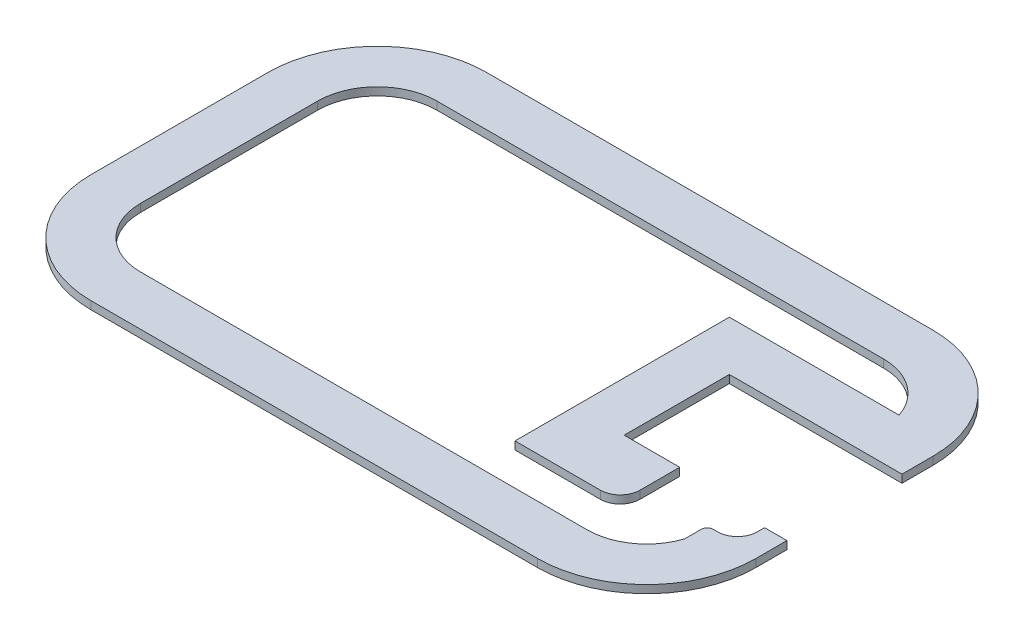
SolidWorks part; units mm, degrees
ref_plane "Front Plane" through (0, 0, 0) normal (0, 0, 1) x (1, 0, 0)
ref_plane "Top Plane" through (0, 0, 0) normal (0, 1, 0) x (1, 0, 0)
ref_plane "Right Plane" through (0, 0, 0) normal (1, 0, 0) x (0, 0, -1)
sketch "Sketch1" plane through (0, 0, 0) normal (0, 1, 0) x (1, 0, 0)
  line L0 (285.2957, -100.4595) -> (285.2957, -116.0895)
  line L1 (5.2657, 28.1705) -> (230.2957, 28.1705)
  line L2 (-49.7343, -26.8295) -> (-49.7343, -116.0895)
  line L3 (5.2657, -171.0895) -> (230.2957, -171.0895)
  line L4 (285.2957, -26.8295) -> (285.2957, -42.4595)
  line L5 (198.2957, -42.4595) -> (285.2957, -42.4595)
  line L6 (198.2957, -42.4595) -> (198.2957, -95.4595)
  line L7 (274.0453, -100.4595) -> (285.2957, -100.4595)
  line L8 (258.7949, -125.4595) -> (258.7949, -125.4595)
  line L9 (5.2657, -146.0895) -> (230.2957, -146.0895)
  line L10 (-24.7343, -26.8295) -> (-24.7343, -116.0895)
  line L11 (5.2657, 3.1705) -> (230.2957, 3.1705)
  line L12 (258.7949, -17.4595) -> (258.7949, -17.4595)
  line L13 (173.2957, -17.4595) -> (258.7949, -17.4595)
  line L14 (173.2957, -17.4595) -> (173.2957, -125.4595)
  line L15 (198.2957, -42.4595) -> (198.2957, -100.4595) construction
  line L16 (274.0453, -100.4595) -> (274.0453, -104.0895)
  line L17 (258.7949, -125.4595) -> (258.7949, -117.0895)
  line L18 (198.2957, -100.4595) -> (285.2957, -100.4595) construction
  line L19 (173.2957, -125.4595) -> (258.7949, -125.4595) construction
  line L20 (173.2957, -125.4595) -> (188.2957, -125.4595)
  line L21 (173.2957, -17.4595) -> (173.2957, -125.4595) construction
  line L22 (264.0453, -114.0895) -> (261.7949, -114.0895)
  line L23 (226.2957, -52.3368) -> (226.2957, -142.322) construction
  line L24 (198.2957, -95.4595) -> (226.2957, -95.4595)
  line L25 (226.2957, -95.4595) -> (226.2957, -115.4595)
  line L26 (216.2957, -125.4595) -> (188.2957, -125.4595)
  arc A0 (5.2657, 28.1705) -> (-49.7343, -26.8295) centre (5.2657, -26.8295) ccw
  arc A1 (-49.7343, -116.0895) -> (5.2657, -171.0895) centre (5.2657, -116.0895) ccw
  arc A2 (230.2957, -171.0895) -> (285.2957, -116.0895) centre (230.2957, -116.0895) ccw
  arc A3 (230.2957, 28.1705) -> (285.2957, -26.8295) centre (230.2957, -26.8295) cw
  arc A4 (230.2957, -146.0895) -> (258.7949, -125.4595) centre (230.2957, -116.0895) ccw
  arc A5 (-24.7343, -116.0895) -> (5.2657, -146.0895) centre (5.2657, -116.0895) ccw
  arc A6 (5.2657, 3.1705) -> (-24.7343, -26.8295) centre (5.2657, -26.8295) ccw
  arc A7 (230.2957, 3.1705) -> (258.7949, -17.4595) centre (230.2957, -26.8295) cw
  arc A8 (226.2957, -115.4595) -> (216.2957, -125.4595) centre (216.2957, -115.4595) cw
  arc A9 (274.0453, -104.0895) -> (264.0453, -114.0895) centre (264.0453, -104.0895) cw
  arc A10 (261.7949, -114.0895) -> (258.7949, -117.0895) centre (261.7949, -117.0895) ccw
  point P6 (-49.7343, 28.1705)
  point P9 (-49.7343, -171.0895)
  point P14 (285.2957, 28.1705)
  point P51 (226.2957, -125.4595)
  dimension "D3" = 55
  dimension "D7" = 10
  dimension "D5" = 10
  dimension "D8" = 3
  dimension "D1" = 335.03
  dimension "D2" = 199.26
  dimension "D4" = 87
  dimension "D9" = 28
  dimension "D10" = 83
  dimension "D6" = 25
extrude "Boss-Extrude1" add sketch "Sketch1" along normal blind 4
